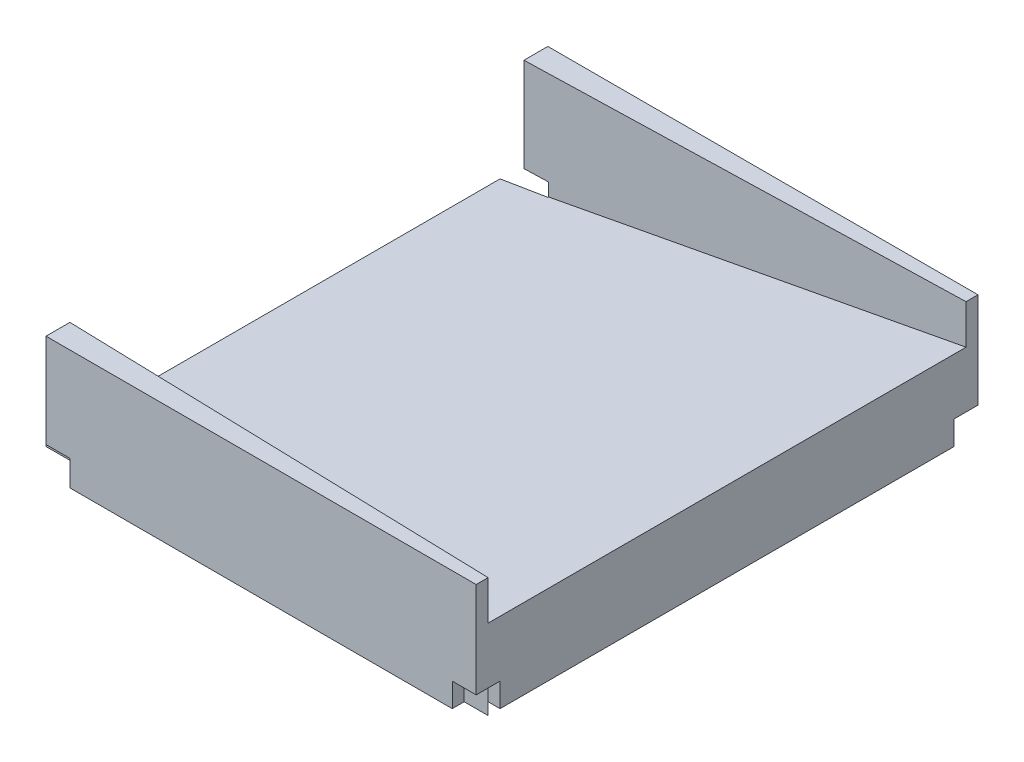
SolidWorks part; units mm, degrees
ref_plane "Plan de face" through (0, 0, 0) normal (0, 0, 1) x (1, 0, 0)
ref_plane "Plan de dessus" through (0, 0, 0) normal (0, 1, 0) x (1, 0, 0)
ref_plane "Plan de droite" through (0, 0, 0) normal (1, 0, 0) x (0, 0, -1)
sketch "Esquisse1" plane through (0, 0, 0) normal (0, 0, 1) x (1, 0, 0)
  line L0 (-105.796, 0) -> (84.204, 0)
  line L1 (84.204, 0) -> (84.204, 33.5021)
  line L3 (-105.796, 0) -> (-105.796, 2)
  line L4 (-105.796, 2) -> (84.204, 33.5021)
  dimension "D1" = 190
  dimension "D2" = 2
extrude "Boss.-Extru.1" add sketch "Esquisse1" along normal blind 200
sketch "Esquisse4" plane through (84.204, 0, 0) normal (1, 0, 0) x (0, 0, -1)
  line L1 (-200, 0) -> (-205, 0)
  line L2 (-200, 0) -> (-200, 50)
  line L3 (-200, 50) -> (-205, 50)
  line L4 (-205, 0) -> (-205, 50)
  line L5 (0, 0) -> (5, 0)
  line L6 (0, 0) -> (0, 50)
  line L7 (0, 50) -> (5, 50)
  line L8 (5, 0) -> (5, 50)
  dimension "D1" = 50
  dimension "D2" = 5
  dimension "D3" = 5
  dimension "D4" = 50
extrude "Boss.-Extru.4" add sketch "Esquisse4" against normal blind 180
sketch "Esquisse8" plane through (0, 50, 0) normal (0, 1, 0) x (1, 0, 0)
  line L0 (84.204, 0) -> (-95.796, 0)
  line L1 (-95.796, 0) -> (-95.796, -5)
  line L2 (-95.796, -5) -> (84.204, 0)
  dimension "D1" = 5
extrude "Boss.-Extru.7" add sketch "Esquisse8" against normal up to surface (50 mm away) up to face at (-54.546, 0, 100.625)
sketch "Esquisse5" plane through (84.204, 0, 0) normal (1, 0, 0) x (0, 0, -1)
  line L1 (-205, 0) -> (-195, 0)
  line L2 (-205, 0) -> (-205, 10)
  line L3 (-205, 10) -> (-195, 10)
  line L4 (-195, 0) -> (-195, 10)
  line L5 (5, 0) -> (-5, 0)
  line L6 (5, 0) -> (5, 10)
  line L7 (5, 10) -> (-5, 10)
  line L8 (-5, 0) -> (-5, 10)
  dimension "D1" = 10
  dimension "D2" = 10
  dimension "D3" = 10
  dimension "D4" = 10
extrude "Enlèv. mat.-Extru.1" cut sketch "Esquisse5" against normal blind 10
ref_plane "Plan2" through (-5.796, 0, 0) normal (1, 0, 0) x (0, 0, -1)
sketch "Esquisse6" plane through (0, 0, -5) normal (0, 0, -1) x (-1, 0, 0)
  line L1 (105.796, 0) -> (85.796, 0)
  line L2 (105.796, 0) -> (105.796, 10.7198)
  line L3 (105.796, 10.7198) -> (85.796, 10.7198)
  line L4 (85.796, 0) -> (85.796, 10.7198)
  line L5 (95.796, 0) -> (95.796, 50) construction
  dimension "D1" = 10
extrude "Enlèv. mat.-Extru.2" cut sketch "Esquisse6" against normal blind 10
ref_plane "Plan3" through (0, 0, 100) normal (0, 0, -1) x (-1, 0, 0)
mirror "Symétrie3" about plane through (0, 0, 100) normal (0, 0, -1) of "Boss.-Extru.7", "Enlèv. mat.-Extru.2"
